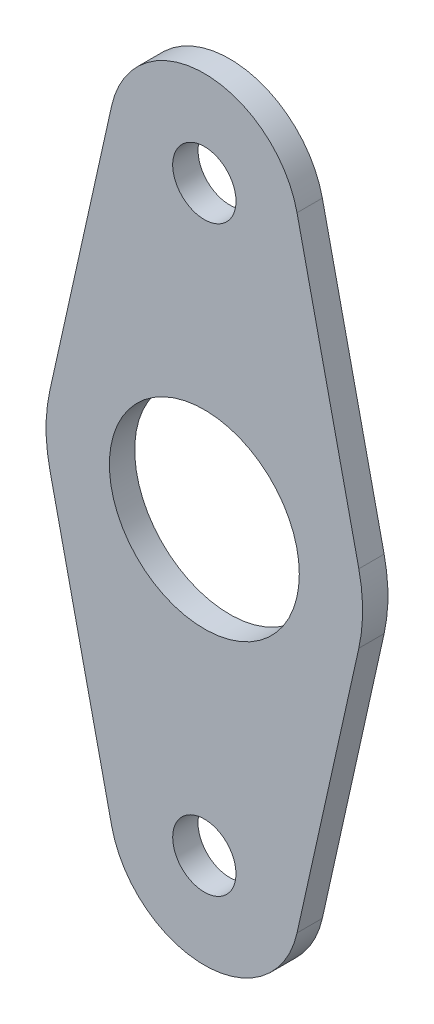
SolidWorks part; units mm, degrees
material "6061-T6 (SS)"
ref_plane "Front Plane" through (0, 0, 0) normal (0, 0, 1) x (1, 0, 0)
ref_plane "Top Plane" through (0, 0, 0) normal (0, 1, 0) x (1, 0, 0)
ref_plane "Right Plane" through (0, 0, 0) normal (1, 0, 0) x (0, 0, -1)
sketch "Sketch1" plane through (0, 0, 0) normal (0, 0, 1) x (1, 0, 0)
  line L0 (0, 0) -> (7.5, 0) construction
  line L1 (-7.3206, 24.6304) -> (-12.2011, 2.7174)
  line L2 (7.3206, 24.6304) -> (12.2011, 2.7174)
  line L3 (7.3206, -24.6304) -> (12.2011, -2.7174)
  line L4 (-7.3206, -24.6304) -> (-12.2011, -2.7174)
  circle A0 centre (0, 0) radius 7.5
  circle A1 centre (0, 23) radius 2.5
  arc A2 (7.3206, 24.6304) -> (-7.3206, 24.6304) centre (0, 23) ccw
  arc A3 (-12.2011, 2.7174) -> (-12.2011, -2.7174) centre (0, 0) ccw
  circle A4 centre (0, -23) radius 2.5
  arc A5 (-7.3206, 24.6304) -> (7.3206, 24.6304) centre (0, 23) ccw construction
  circle A6 centre (0, 23) radius 7.5 construction
  arc A7 (12.2011, 2.7174) -> (-12.2011, 2.7174) centre (0, 0) ccw construction
  circle A8 centre (0, 0) radius 12.5 construction
  arc A9 (7.3206, -24.6304) -> (-7.3206, -24.6304) centre (0, -23) cw
  arc A10 (12.2011, -2.7174) -> (12.2011, 2.7174) centre (0, 0) ccw
  arc A11 (-12.2011, -2.7174) -> (12.2011, -2.7174) centre (0, 0) ccw construction
  point P7 (10.5, 0)
  point P15 (5.5, 23)
  dimension "D1" = 15
  dimension "D2" = 5
  dimension "D3" = 23
  dimension "D4" = 5
extrude "Boss-Extrude1" add sketch "Sketch1" along normal mid plane 2
